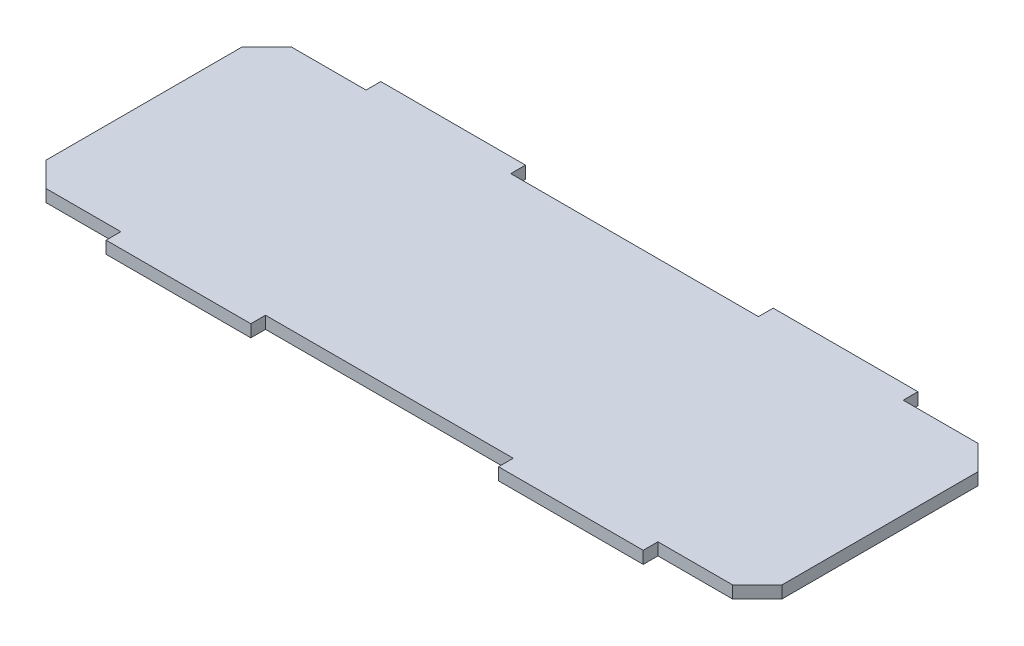
SolidWorks part; units mm, degrees
ref_plane "Alzado" through (0, 0, 0) normal (0, 0, 1) x (1, 0, 0)
ref_plane "Planta" through (0, 0, 0) normal (0, 1, 0) x (1, 0, 0)
ref_plane "Vista lateral" through (0, 0, 0) normal (1, 0, 0) x (0, 0, -1)
sketch "Croquis1" plane through (0, 0, 0) normal (0, 1, 0) x (1, 0, 0)
  line L1 (-70, -25) -> (-54.75, -25)
  line L2 (-75, -20) -> (-75, 20)
  line L3 (-70, 25) -> (-54.75, 25)
  line L4 (75, -20) -> (75, 20)
  line L5 (-75, -25) -> (75, 25) construction
  line L6 (-75, 25) -> (75, -25) construction
  line L8 (-54.75, 25) -> (-54.75, 28)
  line L9 (-54.75, 28) -> (-25.25, 28)
  line L10 (-25.25, 25) -> (-25.25, 28)
  line L12 (-54.75, -25) -> (-54.75, -28)
  line L13 (-54.75, -28) -> (-25.25, -28)
  line L14 (-25.25, -25) -> (-25.25, -28)
  line L16 (25.25, 25) -> (25.25, 28)
  line L17 (25.25, 28) -> (54.75, 28)
  line L18 (54.75, 25) -> (54.75, 28)
  line L20 (25.25, -25) -> (25.25, -28)
  line L21 (25.25, -28) -> (54.75, -28)
  line L22 (54.75, -25) -> (54.75, -28)
  line L24 (54.75, -25) -> (70, -25)
  line L25 (54.75, 25) -> (70, 25)
  line L26 (0, 0) -> (0, 53.7468) construction
  line L27 (-75, 20) -> (-70, 25)
  line L28 (-75, -20) -> (-70, -25)
  line L29 (70, -25) -> (75, -20)
  line L30 (70, 25) -> (75, 20)
  line L55 (-25.25, 25) -> (25.25, 25)
  line L56 (-25.25, -25) -> (25.25, -25)
  point P0 (0, 0)
  point P22 (-40, 28)
  point P23 (-40, -28)
  point P26 (40, 28)
  dimension "D1" = 50
  dimension "D2" = 150
  dimension "D3" = 40
  dimension "D4" = 29.5
  dimension "D5" = 40
  dimension "D6" = 3
extrude "Saliente-Extruir1" add sketch "Croquis1" along normal blind 2.5
